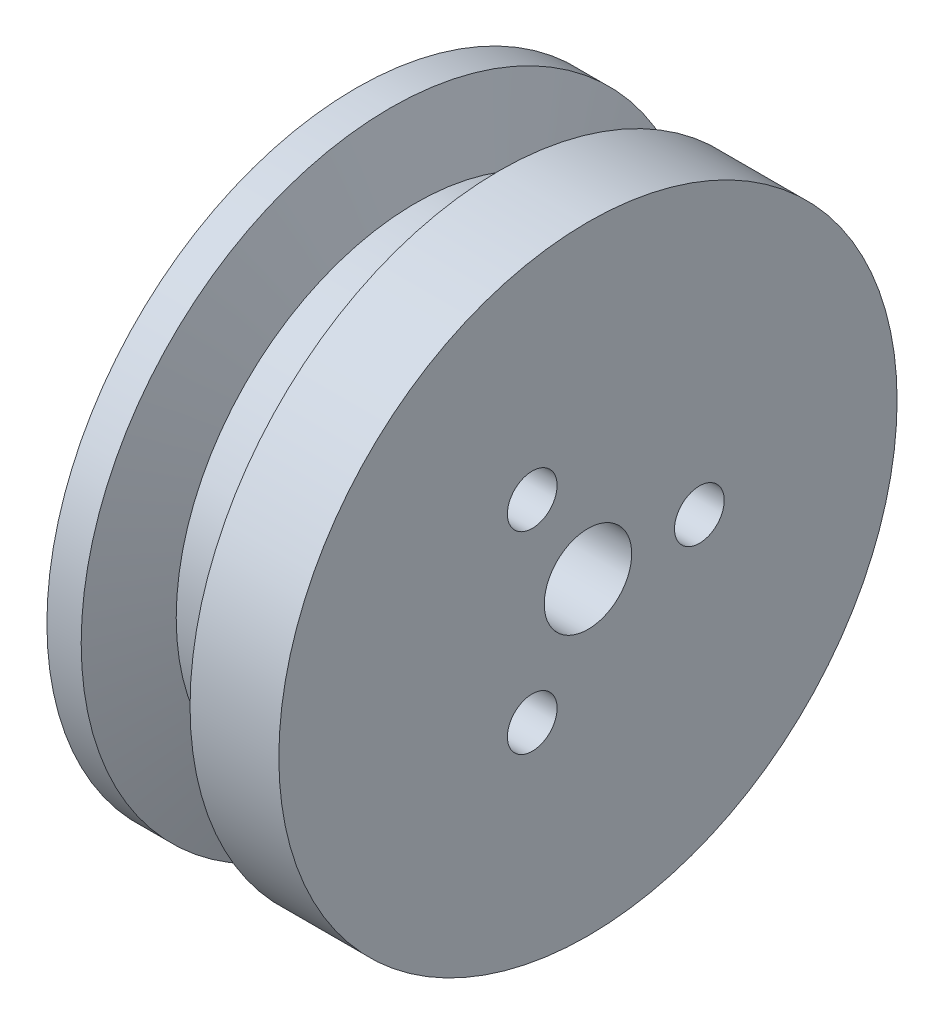
SolidWorks part; units mm, degrees
ref_plane "Front" through (0, 0, 0) normal (0, 0, 1) x (1, 0, 0)
ref_plane "Top" through (0, 0, 0) normal (0, 1, 0) x (1, 0, 0)
ref_plane "Right" through (0, 0, 0) normal (1, 0, 0) x (0, 0, -1)
sketch "Sketch1" plane through (0, 0, 0) normal (0, 0, 1) x (1, 0, 0)
  line L0 (0, 0) -> (11.2549, 0) construction
  line L1 (0, 0) -> (0, 18.034)
  line L2 (0, 18.034) -> (2, 18.034)
  line L3 (2, 18.034) -> (3.4792, 13.97)
  line L4 (3.4792, 13.97) -> (6.8708, 13.97)
  line L5 (8.35, 18.034) -> (13.53, 18.034)
  line L6 (6.8708, 13.97) -> (8.35, 18.034)
  line L7 (13.53, 18.034) -> (13.53, 2.55)
  line L8 (8.53, 2.55) -> (13.53, 2.55)
  line L9 (5.175, 13.97) -> (5.175, 2.55) construction
  line L11 (0, 0) -> (8.53, 0)
  line L12 (8.53, 0) -> (8.53, 2.55)
  dimension "D1" = 6.35
  dimension "D2" = 40
  dimension "D3" = 5.1
  dimension "D4" = 5
  dimension "D5" = 5.18
  dimension "D6" = 36.068
  dimension "D7" = 2
  dimension "D8" = 4.064
revolve "Revolve1" add sketch "Sketch1" angle 360 about L0
sketch "Sketch2" plane through (0, 0, 0) normal (-1, 0, 0) x (0, 0, 1)
  circle A0 centre (0, 0) radius 6.5 construction
  dimension "D1" = 13
hole_wizard "CBORE for M2.5 SHCS1" positions "Sketch5" profile "Sketch6" counterbore size "M2.5" standard "ANSI Metric" end condition through all
sketch "Sketch5" plane through (0, 0, 0) normal (-1, 0, 0) x (0, 0, 1)
  circle A0 centre (0, 0) radius 6.5 construction
  point P0 (-6.5, 0)
  point P8 (3.25, 5.6292)
  point P9 (3.25, -5.6292)
  dimension "D1" = 3
sketch "Sketch6" plane through (0, 0, -6.5) normal (0, 1, 0) x (0, 0, 1)
  line L0 (0, 0) -> (0, 13.53)
  line L1 (0, 13.53) -> (1.45, 13.53)
  line L3 (1.45, 13.53) -> (1.45, 2.5)
  line L4 (1.45, 2.5) -> (2.75, 2.5)
  line L5 (2.75, 2.5) -> (2.75, 0)
  line L7 (2.75, 0) -> (0, 0)
  line L11 (0, -6.35) -> (0, 107.95) construction
  dimension "Thru Hole Dia." = 2.9
  dimension "Thru Hole Depth" = 13.53
  dimension "C'Bore Dia." = 5.5
  dimension "C'Bore Depth" = 2.5
hole_wizard "#10-32 Tapped Hole1" positions "Sketch7" profile "Sketch9" tap size "#10-32" standard "ANSI Inch" end condition through all
sketch "Sketch7" plane through (0, 0, 0) normal (-1, 0, 0) x (0, 0, 1)
  point P0 (0, 0)
sketch "Sketch9" plane through (0, 0, 0) normal (0, 1, 0) x (0, 0, 1)
  line L0 (0, 0) -> (0, 13.53)
  line L1 (0, 13.53) -> (2.0193, 13.53)
  line L2 (2.0193, 13.53) -> (2.0193, 0)
  line L5 (2.0193, 0) -> (0, 0)
  line L11 (0, -6.35) -> (0, 107.95) construction
  dimension "Thru Tap Drill Dia." = 4.0386
  dimension "Thru Tap Drill Depth" = 13.53
cosmetic thread "Hole Thread1" parameters "D2"=4.826
ref_plane "Plane1" through (5.175, 0, 0) normal (-1, 0, 0) x (0, 0, 1)
